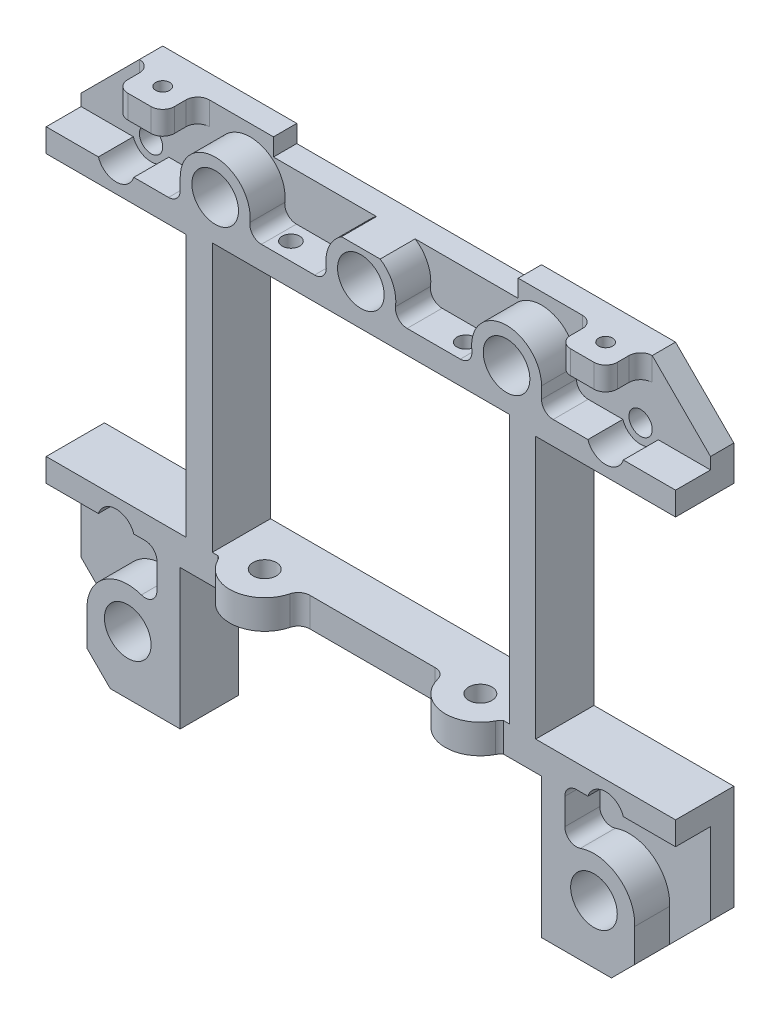
SolidWorks part; units mm, degrees
ref_plane "前视基准面" through (0, 0, 0) normal (0, 0, 1) x (1, 0, 0)
ref_plane "上视基准面" through (0, 0, 0) normal (0, 1, 0) x (1, 0, 0)
ref_plane "右视基准面" through (0, 0, 0) normal (1, 0, 0) x (0, 0, -1)
sketch "草图1" plane through (0, 0, 0) normal (0, 0, 1) x (1, 0, 0)
  line L0 (0, 54.5254) -> (0, -46.9226) construction
  line L1 (77.1188, 0) -> (-86.5987, 0) construction
  line L2 (-27, 25) -> (-15, 25)
  line L3 (-15, 25) -> (-15, 2.5)
  line L4 (-15, 2.5) -> (-27, 2.5)
  line L5 (-27, 2.5) -> (-27, -6.5)
  line L6 (-27, -6.5) -> (-21.5, -12)
  line L7 (-21.5, -12) -> (-15.5, -12)
  line L8 (-15.5, -12) -> (-15.5, 0)
  line L9 (-15.5, 0) -> (15.5, 0)
  line L10 (-27, 25) -> (-27, 28)
  line L11 (-22, 33) -> (22, 33)
  line L12 (-12.75, 25.5) -> (-12.75, 2.5)
  line L13 (-12.75, 2.5) -> (12.75, 2.5)
  line L14 (12.75, 25.5) -> (-12.75, 25.5)
  line L15 (15.5, -12) -> (15.5, 0)
  line L16 (21.5, -12) -> (15.5, -12)
  line L17 (15, 2.5) -> (27, 2.5)
  line L18 (27, 2.5) -> (27, -6.5)
  line L19 (15, 25) -> (15, 2.5)
  line L20 (27, 25) -> (27, 28)
  line L21 (12.75, 25.5) -> (12.75, 2.5)
  line L22 (15, 25) -> (27, 25)
  line L23 (21.5, -12) -> (27, -6.5)
  line L24 (-27, 28) -> (-22, 33)
  line L25 (27, 28) -> (22, 33)
  circle A0 centre (20, -7) radius 2
  circle A1 centre (12.5, 29) radius 2
  circle A2 centre (0, 29) radius 2
  circle A3 centre (-20, -7) radius 2
  circle A4 centre (-12.5, 29) radius 2
  circle A5 centre (21, 27.5) radius 1
  circle A6 centre (21, 0) radius 1
  circle A7 centre (-21, 27.5) radius 1
  circle A8 centre (-21, 0) radius 1
  point P36 (0, 36)
  point P37 (-27, 33)
  point P40 (0, 0)
  point P41 (0, 0)
  point P48 (27, 33)
  point P50 (0, 25.5)
  dimension "D1" = 4
  dimension "D2" = 4
  dimension "D3" = 4
  dimension "D10" = 2
  dimension "D11" = 2
  dimension "D4" = 27.5
  dimension "D5" = 42
  dimension "D6" = 40
  dimension "D7" = 25
  dimension "D8" = 7
  dimension "D9" = 27.5
  dimension "D12" = 29
  dimension "D13" = 15.5
  dimension "D14" = 2.5
  dimension "D15" = 6
  dimension "D16" = 2.5
  dimension "D17" = 25.5
  dimension "D18" = 6
  dimension "D19" = 6
  dimension "D20" = 12
  dimension "D21" = 2.5
  dimension "D23" = 45
  dimension "D24" = 25.5
extrude "凸台-拉伸1" add sketch "草图1" along normal blind 2
sketch "草图3" plane through (0, 2.5, 0) normal (0, 1, 0) x (1, 0, 0)
  line L0 (0, 0) -> (0, -8.4944) construction
  line L1 (22, 0) -> (-22, 0) construction
  line L2 (-9.25, 1.7097) -> (-9.25, -4) construction
  line L3 (-6.25, -2) -> (-6.25, -4)
  line L4 (22, -2) -> (-22, -2) construction
  line L5 (-12.25, -2) -> (-12.25, -4)
  line L6 (-12.25, -2) -> (-6.25, -2)
  line L7 (12.25, -2) -> (6.25, -2)
  line L8 (12.25, -2) -> (12.25, -4)
  line L9 (6.25, -2) -> (6.25, -4)
  circle A0 centre (-9.25, -4) radius 1
  arc A1 (-12.25, -4) -> (-6.25, -4) centre (-9.25, -4) ccw
  arc A2 (12.25, -4) -> (6.25, -4) centre (9.25, -4) cw
  circle A3 centre (9.25, -4) radius 1
  dimension "D3" = 2
  dimension "D4" = 3
  dimension "D1" = 4
  dimension "D2" = 18.5
extrude "凸台-拉伸2" add sketch "草图3" against normal blind 2.5
sketch "草图4" plane through (0, 0, 2) normal (0, 0, 1) x (1, 0, 0)
  line L2 (-15.5, 29) -> (-15.5, 27)
  line L5 (-9.9019, 27.5) -> (-2.5981, 27.5)
  line L9 (2.5981, 27.5) -> (9.9019, 27.5)
  line L10 (15.5, 29) -> (15.5, 27)
  line L11 (-19.4801, 0.5) -> (-17.5, 0.5)
  line L12 (-17.5, 0.5) -> (-17.5, -4.5505)
  line L14 (-22.5199, 0.5) -> (-25, 0.5)
  line L15 (-25, 0.5) -> (-25, -5.6716) construction
  line L16 (-25, -5.6716) -> (-23.4956, -7.176) construction
  line L17 (0, 0) -> (0, -5.4356) construction
  line L18 (19.4801, 0.5) -> (17.5, 0.5)
  line L19 (17.5, 0.5) -> (17.5, -4.5505)
  line L21 (25, -5.6716) -> (23.4956, -7.176) construction
  line L22 (25, 0.5) -> (25, -5.6716) construction
  line L23 (22.5199, 0.5) -> (25, 0.5)
  line L24 (25, 0.5) -> (27, 0.5)
  line L25 (-25, 0.5) -> (-27, 0.5)
  line L26 (-23.4956, -7.176) -> (-23.4956, -10.0044)
  line L27 (23.4956, -7.176) -> (23.4956, -10.0044)
  line L28 (-15.5, 27) -> (-19.4801, 27)
  line L30 (-27, 27) -> (-27, 25)
  line L31 (-27, 25) -> (-16.5, 25)
  line L32 (27, 25) -> (16.5, 25)
  line L33 (15.5, 27) -> (19.4801, 27)
  line L34 (27, 27) -> (27, 25)
  line L35 (12.25, 2.5) -> (12.25, 0)
  line L36 (12.25, 0) -> (15.5, 0)
  line L37 (15.5, 0) -> (15.5, -12)
  line L38 (15.5, -12) -> (21.5, -12)
  line L39 (21.5, -12) -> (27, -6.5)
  line L40 (27, -6.5) -> (27, 2.5)
  line L41 (27, 2.5) -> (15, 2.5)
  line L42 (15, 2.5) -> (15, 25)
  line L43 (15, 25) -> (27, 25)
  line L44 (27, 25) -> (27, 28)
  line L45 (27, 28) -> (22, 33)
  line L46 (22, 33) -> (-22, 33)
  line L47 (-22, 33) -> (-27, 28)
  line L48 (-27, 28) -> (-27, 25)
  line L49 (-27, 25) -> (-15, 25)
  line L50 (-15, 25) -> (-15, 2.5)
  line L51 (-15, 2.5) -> (-27, 2.5)
  line L52 (-27, 2.5) -> (-27, -6.5)
  line L53 (-27, -6.5) -> (-21.5, -12)
  line L54 (-21.5, -12) -> (-15.5, -12)
  line L55 (-15.5, -12) -> (-15.5, 0)
  line L84 (-15.5, 0) -> (-12.25, 0)
  line L85 (-12.25, 0) -> (-12.25, 2.5)
  line L86 (-12.25, 2.5) -> (-12.75, 2.5)
  line L87 (-12.75, 2.5) -> (-12.75, 25.5)
  line L88 (-12.75, 25.5) -> (12.75, 25.5)
  line L89 (12.75, 25.5) -> (12.75, 2.5)
  line L90 (12.75, 2.5) -> (12.25, 2.5)
  line L91 (12.25, 2.5) -> (12.25, 0)
  line L92 (12.25, 0) -> (15.5, 0)
  line L93 (15.5, 0) -> (15.5, -12)
  line L94 (15.5, -12) -> (21.5, -12)
  line L95 (21.5, -12) -> (23.4956, -10.0044)
  line L96 (27, 0.5) -> (27, 2.5)
  line L97 (27, 2.5) -> (15, 2.5)
  line L98 (15, 2.5) -> (15, 25)
  line L99 (15, 25) -> (16.5, 25)
  line L105 (-16.5, 25) -> (-15, 25)
  line L106 (-15, 25) -> (-15, 2.5)
  line L107 (-15, 2.5) -> (-27, 2.5)
  line L108 (-27, 2.5) -> (-27, 0.5)
  line L109 (-23.4956, -10.0044) -> (-21.5, -12)
  line L110 (-21.5, -12) -> (-15.5, -12)
  line L111 (-15.5, -12) -> (-15.5, 0)
  line L112 (-15.5, 0) -> (-12.25, 0)
  line L113 (-12.25, 0) -> (-12.25, 2.5)
  line L114 (-12.25, 2.5) -> (-12.75, 2.5)
  line L115 (-12.75, 2.5) -> (-12.75, 25.5)
  line L116 (-12.75, 25.5) -> (12.75, 25.5)
  line L117 (12.75, 25.5) -> (12.75, 2.5)
  line L118 (12.75, 2.5) -> (12.25, 2.5)
  line L119 (-22.5199, 27) -> (-27, 27)
  line L120 (22.5199, 27) -> (27, 27)
  line L121 (-21, 33) -> (-21, 31)
  line L122 (22, 33) -> (-22, 33) construction
  line L123 (-17, 33) -> (-17, 31)
  line L124 (-17, 31) -> (-21, 31)
  line L125 (-17, 33) -> (-21, 33)
  line L126 (17, 33) -> (21, 33)
  line L127 (17, 31) -> (21, 31)
  line L128 (17, 33) -> (17, 31)
  line L129 (21, 33) -> (21, 31)
  arc A2 (-19.4801, 0.5) -> (-22.5199, 0.5) centre (-21, 0) ccw
  arc A3 (22.5199, 0.5) -> (19.4801, 0.5) centre (21, 0) ccw
  circle A5 centre (-20, -7) radius 2 construction
  circle A6 centre (20, -7) radius 2 construction
  circle A7 centre (12.5, 29) radius 2 construction
  circle A8 centre (0, 29) radius 2 construction
  circle A9 centre (-12.5, 29) radius 2 construction
  circle A10 centre (20, -7) radius 2
  circle A11 centre (12.5, 29) radius 2
  circle A12 centre (0, 29) radius 2
  circle A13 centre (-12.5, 29) radius 2
  circle A14 centre (-20, -7) radius 2
  arc A15 (-9.9019, 27.5) -> (-15.5, 29) centre (-12.5, 29) ccw
  arc A16 (2.5981, 27.5) -> (-2.5981, 27.5) centre (0, 29) ccw
  arc A17 (15.5, 29) -> (9.9019, 27.5) centre (12.5, 29) ccw
  arc A18 (-23.4956, -7.176) -> (-17.5, -4.5505) centre (-20, -7) cw
  arc A19 (23.4956, -7.176) -> (17.5, -4.5505) centre (20, -7) ccw
  arc A20 (-22.5199, 27) -> (-19.4801, 27) centre (-21, 27.5) ccw
  arc A21 (22.5199, 27) -> (19.4801, 27) centre (21, 27.5) cw
  dimension "D2" = 2
  dimension "D3" = 2
  dimension "D4" = 3.2
  dimension "D5" = 3.2
  dimension "D6" = 4
  dimension "D7" = 6
  dimension "D8" = 6
  dimension "D12" = 1.5
  dimension "D14" = 3.2
  dimension "D9" = 2
  dimension "D10" = 2
  dimension "D11" = 2
  dimension "D13" = 2
  dimension "D15" = 2
  dimension "D1" = 0
extrude "凸台-拉伸3" add sketch "草图4" along normal blind 3
fillet "圆角1" radius 1 18 edges at (17.5, 0.5, 3.5) (17.5, -4.5505, 3.5) (-17.5, -4.5505, 3.5) (-17.5, 0.5, 3.5) (9.9019, 27.5, 3.5) (2.5981, 27.5, 3.5) (-2.5981, 27.5, 3.5) (-9.9019, 27.5, 3.5) (15.5, 27, 3.5) (-15.5, 27, 3.5) (-21, 32, 5) (-17, 32, 5) (17, 32, 5) (21, 32, 5) (21, 32, 2) (17, 32, 2) (-17, 32, 2) (-21, 32, 2)
fillet "圆角2" radius 1 2 edges at (-12.25, 1.25, 4) (12.25, 1.25, 4)
sketch "草图5" plane through (0, 0, 2) normal (0, 0, 1) x (1, 0, 0)
  line L4 (6.25, 0) -> (6.25, 2.5)
  line L5 (6.25, 2.5) -> (-6.25, 2.5)
  line L6 (-6.25, 2.5) -> (-6.25, 0)
  line L7 (-6.25, 0) -> (6.25, 0)
  line L8 (6.25, 0) -> (6.25, 2.5)
  line L9 (6.25, 2.5) -> (-6.25, 2.5)
  line L10 (-6.25, 2.5) -> (-6.25, 0)
  line L11 (-6.25, 0) -> (6.25, 0)
  dimension "D1" = 0
extrude "凸台-拉伸4" add sketch "草图5" along normal blind 2
fillet "圆角3" radius 1 2 edges at (6.25, 1.25, 4) (-6.25, 1.25, 4)
sketch "草图6" plane through (0, 0, 0) normal (0, -1, 0) x (1, 0, 0)
  circle A0 centre (-9.25, 4) radius 2
  circle A1 centre (9.25, 4) radius 2
  dimension "D1" = 4
  dimension "D2" = 4
extrude "切除-拉伸1" cut sketch "草图6" against normal blind 1
sketch "草图7" plane through (0, -12, 0) normal (0, -1, 0) x (1, 0, 0)
  line L0 (0, 0) -> (0, 11.3884) construction
  line L1 (-15.5, 0) -> (15.5, 0) construction
  circle A0 centre (19, 2.5) radius 0.75
  circle A1 centre (-19, 2.5) radius 0.75
  dimension "D1" = 1.5
  dimension "D2" = 19
  dimension "D3" = 2.5
extrude "切除-拉伸2" cut sketch "草图7" against normal blind 2.5
sketch "草图8" plane through (0, 33, 0) normal (0, 1, 0) x (1, 0, 0)
  line L0 (0, 0) -> (0, -8.4556) construction
  line L1 (20, -5) -> (18, -5) construction
  circle A0 centre (-19, -3) radius 0.6
  circle A1 centre (19, -3) radius 0.6
  dimension "D3" = 1.2
  dimension "D1" = 19
  dimension "D2" = 2
extrude "切除-拉伸3" cut sketch "草图8" against normal blind 3
sketch "Sketch1" plane through (0, 33, 0) normal (0, 1, 0) x (1, 0, 0)
  line L0 (0, 8.1238) -> (0, -11.5813) construction
  line L1 (10.5, 2) -> (-10.5, 2)
  line L2 (-10.5, 2) -> (-10.5, -8)
  line L3 (-10.5, -8) -> (10.5, -8)
  line L4 (10.5, 2) -> (10.5, -8)
  point P8 (0, -8)
  point P9 (0, 2)
  dimension "D1" = 21
  dimension "D2" = 10
  dimension "D3" = 2
extrude "Cut-Extrude1" cut sketch "Sketch1" against normal blind 1.5
sketch "Sketch3" plane through (0, 27.5, 0) normal (0, 1, 0) x (1, 0, 0)
  line L0 (0, 7.0168) -> (0, -9.8101) construction
  line L1 (-3.9686, -5) -> (-8.5314, -5) construction
  circle A0 centre (-7.5, -3.5) radius 0.75
  circle A1 centre (7.5, -3.5) radius 0.75
  dimension "D1" = 1.5
  dimension "D2" = 15
  dimension "D3" = 1.5
extrude "Cut-Extrude2" cut sketch "Sketch3" against normal blind 11
